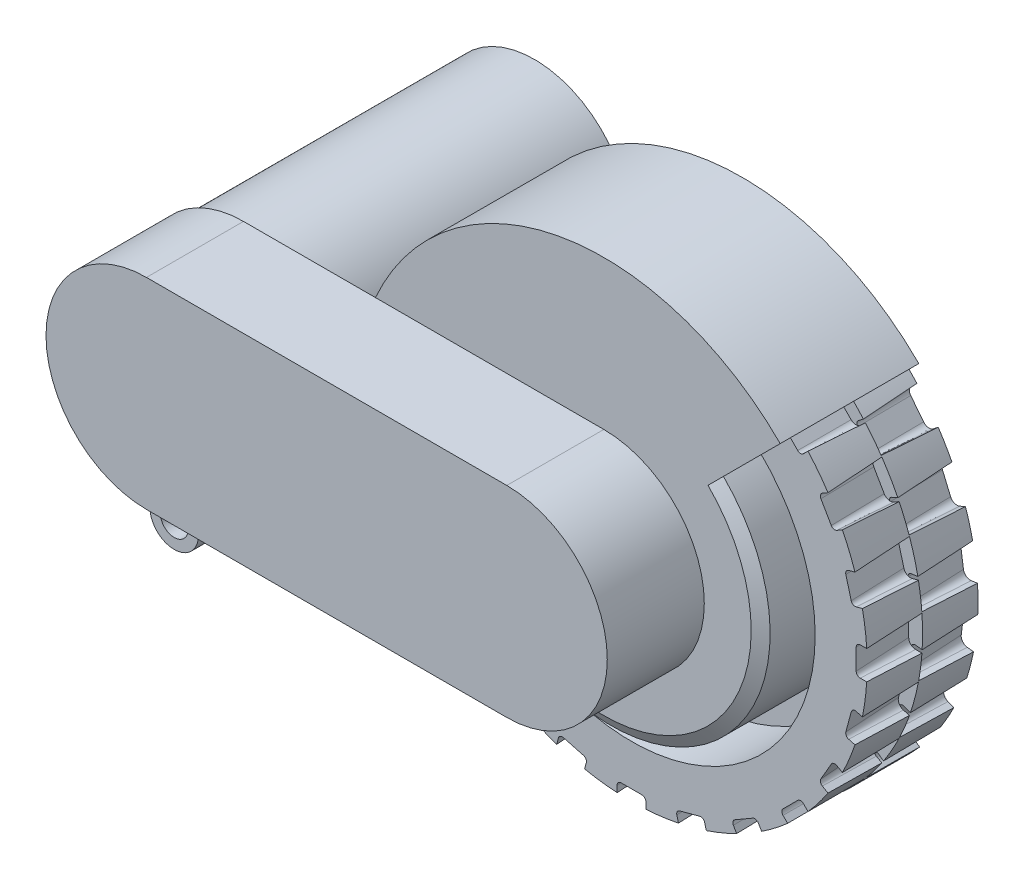
SolidWorks part; units mm, degrees
ref_plane "前视基准面" through (0, 0, 0) normal (0, 0, 1) x (1, 0, 0)
ref_plane "上视基准面" through (0, 0, 0) normal (0, 1, 0) x (1, 0, 0)
ref_plane "右视基准面" through (0, 0, 0) normal (1, 0, 0) x (0, 0, -1)
sketch "草图1" plane through (0, 0, 0) normal (0, 0, 1) x (1, 0, 0)
  circle A0 centre (0, 0) radius 34
  circle A1 centre (0, 0) radius 1.5
  dimension "D1" = 68
  dimension "D2" = 3
extrude "凸台-拉伸1" add sketch "草图1" along normal blind 8
sketch "草图2" plane through (0, 0, 8) normal (0, 0, 1) x (1, 0, 0)
  line L0 (0, 36.7804) -> (0, -36.1417) construction
  line L2 (-2.5, 34.6196) -> (2.5, 34.6196)
  line L3 (-2.5, 34.6196) -> (-2.5, 33)
  line L4 (-1.5, 32) -> (1.5, 32)
  line L5 (2.5, 34.6196) -> (2.5, 33)
  circle A0 centre (0, 0) radius 34 construction
  arc A1 (1.5, 32) -> (2.5, 33) centre (1.5, 33) ccw
  arc A2 (-2.5, 33) -> (-1.5, 32) centre (-1.5, 33) ccw
  point P11 (2.5, 32)
  point P14 (-2.5, 32)
  dimension "D4" = 1
  dimension "D1" = 5
  dimension "D2" = 2.5
  dimension "D3" = 32
extrude "切除-拉伸1" cut sketch "草图2" against normal through all draft 3
pattern_circular "阵列(圆周)1" count 24 over 360 about axis through (0, 0, 8) along (0, 0, 1) of "切除-拉伸1"
move or copy body "实体-移动/复制1" bodies to move or copy 108 copy yes number of copies 1 translate (0, 0, 8)
move or copy body "实体-移动/复制2" bodies to move or copy 110 copy no rotation origin (0, 0, 0) rotation axis (0, 0, 1) rotation angle 8
sketch "草图3" plane through (0, 0, 16) normal (0, 0, 1) x (1, 0, 0)
  circle A0 centre (0, 0) radius 5
  dimension "D1" = 10
extrude "切除-拉伸2" cut sketch "草图3" against normal blind 3
sketch "草图4" plane through (0, 0, 16) normal (0, 0, 1) x (1, 0, 0)
  circle A0 centre (0, 0) radius 13
  circle A1 centre (0, 0) radius 14.5
  circle A2 centre (0, 0) radius 27.5
  circle A3 centre (0, 0) radius 26
  dimension "D1" = 29
  dimension "D2" = 55
  dimension "D3" = 1.5
extrude "切除-拉伸3" cut sketch "草图4" against normal blind 0.5 contours A1 A0 | A2 A3 region at (-14.0899, 0, 16) region at (-26.7222, 0, 16)
sketch "草图5" plane through (0, 0, 0) normal (0, 0, -1) x (-1, 0, 0)
  circle A0 centre (0, 0) radius 26.5
  dimension "D1" = 53
extrude "切除-拉伸4" cut sketch "草图5" against normal blind 10
sketch "草图6" plane through (0, 0, 10) normal (0, 0, -1) x (-1, 0, 0)
  circle A0 centre (0, 0) radius 23
  dimension "D1" = 46
extrude "凸台-拉伸2" add sketch "草图6" along normal blind 13
sketch "草图7" plane through (0, 0, -3) normal (0, 0, -1) x (-1, 0, 0)
  circle A2 centre (0, 0) radius 23
  circle A3 centre (0, 0) radius 23
  dimension "D1" = 0
extrude "凸台-拉伸3" add sketch "草图7" along normal blind 1 draft 60
sketch "草图8" plane through (0, 0, -4) normal (0, 0, -1) x (-1, 0, 0)
  line L0 (-15.0387, 15.0387) -> (-25.4558, 25.4558)
  line L1 (15.5588, -14.5) -> (-15.0387, 15.0387)
  line L2 (0, 42.7879) -> (0, -11.5413) construction
  line L3 (15.5588, -14.5) -> (32.9507, -14.5)
  arc A0 (32.9507, -14.5) -> (-25.4558, 25.4558) centre (0, 0) ccw
  dimension "D1" = 72
  dimension "D3" = 14.5
  dimension "D4" = 45
extrude "凸台-拉伸4" add sketch "草图8" against normal blind 2
sketch "草图9" plane through (0, 0, -2) normal (0, 0, 1) x (1, 0, 0)
  line L0 (24.7487, 24.7487) -> (25.4558, 25.4558)
  line L1 (-32.9507, -14.5) -> (-32.0354, -14.0972)
  arc A0 (25.4558, 25.4558) -> (-32.9507, -14.5) centre (0, 0) ccw construction
  arc A1 (25.4558, 25.4558) -> (-32.9507, -14.5) centre (0, 0) ccw
  arc A2 (24.7487, 24.7487) -> (-32.0354, -14.0972) centre (0, 0) ccw
  dimension "D1" = 1
extrude "凸台-拉伸5" add sketch "草图9" along normal up to surface (18 mm away)
sketch "草图10" plane through (0, 0, -4) normal (0, 0, -1) x (-1, 0, 0)
  line L1 (0, 14.5) -> (52, 14.5)
  line L3 (0, -14.5) -> (52, -14.5)
  arc A0 (0, 14.5) -> (0, -14.5) centre (0, 0) ccw
  arc A1 (52, -14.5) -> (52, 14.5) centre (52, 0) ccw
  dimension "D1" = 29
  dimension "D2" = 14.5
  dimension "D3" = 52
extrude "凸台-拉伸6" add sketch "草图10" along normal blind 14
sketch "草图11" plane through (0, 0, -4) normal (0, 0, 1) x (1, 0, 0)
  circle A0 centre (-52, 0) radius 13.75
  dimension "D1" = 27.5
extrude "凸台-拉伸7" add sketch "草图11" along normal blind 42
sketch "草图12" plane through (0, 0, -18) normal (0, 0, -1) x (-1, 0, 0)
  line L0 (49.5, -19) -> (49.5, -13.4164)
  line L1 (49.5, -13.4164) -> (57.5, -13.4164)
  line L2 (57.5, -13.4164) -> (56.4224, -19.7331)
  circle A0 centre (53, -19) radius 2
  arc A1 (0, 14.5) -> (0, -14.5) centre (0, 0) ccw construction
  arc A2 (49.5, -19) -> (56.4718, -19.443) centre (53, -19) ccw
  arc A3 (52, -14.5) -> (52, 14.5) centre (52, 0) ccw construction
  line M2 (0, -14.5) -> (52, -14.5)
  arc M3 (52, -14.5) -> (52, 14.5) centre (52, 0) ccw
  dimension "D1" = 4
  dimension "D2" = 53
  dimension "D3" = 19
  dimension "D4" = 7
  dimension "D5" = 8
extrude "凸台-拉伸8" add sketch "草图12" against normal blind 25 from offset 5 contours L1 L0 M2 M3 | L0 A2 L2 A0 M3 M2 region at (-49.621, -16.75, -18) region at (-52.7321, -13.8944, -18) offset against normal yes
mirror "镜向6" about plane through (-52, 0, 38) normal (0, 0, 1) of bodies 122
sketch "草图13" plane through (0, 0, -18) normal (0, 0, -1) x (-1, 0, 0)
  line L1 (-52.3399, 49.7072) -> (90.9415, 49.7072)
  line L2 (-52.3399, 49.7072) -> (-52.3399, -47.0761)
  line L3 (-52.3399, -47.0761) -> (90.9415, -47.0761)
  line L4 (90.9415, 49.7072) -> (90.9415, -47.0761)
extrude "切除-拉伸5" cut sketch "草图13" against normal blind 56
